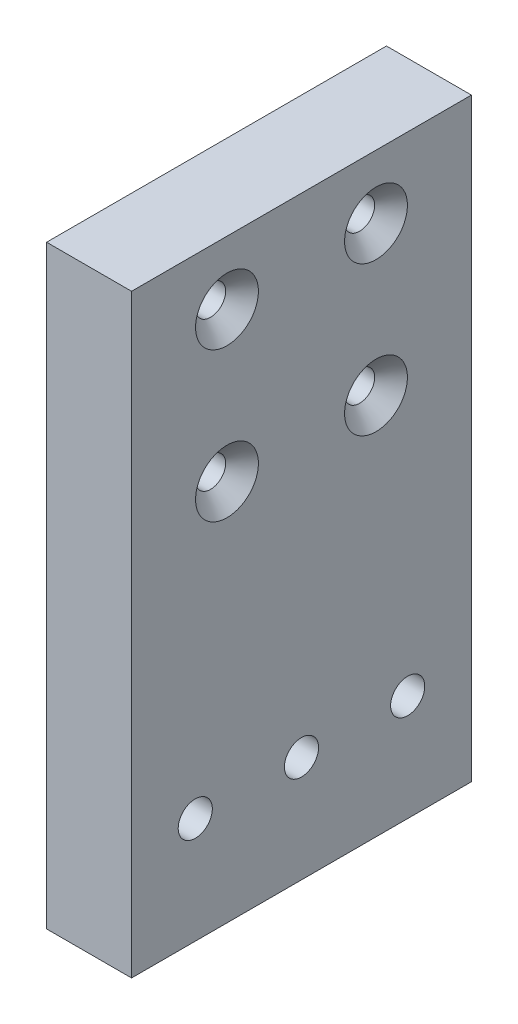
SolidWorks part; units mm, degrees
material "Nylon 6/10"
ref_plane "Front Plane" through (0, 0, 0) normal (0, 0, 1) x (1, 0, 0)
ref_plane "Top Plane" through (0, 0, 0) normal (0, 1, 0) x (1, 0, 0)
ref_plane "Right Plane" through (0, 0, 0) normal (1, 0, 0) x (0, 0, -1)
sketch "Sketch1" plane through (0, 0, 0) normal (1, 0, 0) x (0, 0, -1)
  line L1 (-25.4, -44.45) -> (25.4, -44.45)
  line L2 (-25.4, -44.45) -> (-25.4, 44.45)
  line L3 (-25.4, 44.45) -> (25.4, 44.45)
  line L4 (25.4, -44.45) -> (25.4, 44.45)
  line L5 (-25.4, -44.45) -> (25.4, 44.45) construction
  line L6 (-25.4, 44.45) -> (25.4, -44.45) construction
  point P0 (0, 0)
  dimension "D1" = 50.8
  dimension "D2" = 88.9
extrude "Boss-Extrude1" add sketch "Sketch1" along normal blind 12.7
hole_wizard "CSK for M4 Flat Head Machine Screw1" positions "Sketch3" profile "Sketch2" countersink size "M4" standard "ANSI Metric" end condition through all
sketch "Sketch3" plane through (12.7, 0, 0) normal (1, 0, 0) x (0, 0, -1)
  line L1 (-11.1369, 12.7) -> (11.1369, 12.7) construction
  line L2 (-11.1369, 12.7) -> (-11.1369, 34.9739) construction
  line L3 (-11.1369, 34.9739) -> (11.1369, 34.9739) construction
  line L4 (11.1369, 12.7) -> (11.1369, 34.9739) construction
  line L5 (-11.1369, 12.7) -> (11.1369, 34.9739) construction
  line L6 (-11.1369, 34.9739) -> (11.1369, 12.7) construction
  line L8 (25.4, 44.45) -> (-25.4, 44.45) construction
  point P219 (11.1369, 34.9739)
  point P223 (-11.1369, 34.9739)
  point P225 (-11.1369, 12.7)
  point P227 (11.1369, 12.7)
  dimension "D1" = 31.5
  dimension "D2" = 31.75
sketch "Sketch2" plane through (12.7, 34.9739, -11.1369) normal (0, 1, 0) x (0, 0, -1)
  line L0 (0, 0) -> (0, 12.7)
  line L1 (0, 12.7) -> (2.25, 12.7)
  line L2 (2.25, 12.7) -> (2.25, 2.45)
  line L3 (2.25, 2.45) -> (4.7, 0)
  line L5 (4.7, 0) -> (0, 0)
  line L6 (-2.25, 2.45) -> (-4.7, 0) construction
  line L11 (0, -6.35) -> (0, 107.95) construction
  dimension "Thru Hole Dia." = 4.5
  dimension "Thru Hole Depth" = 12.7
  dimension "Near C'Sink Dia." = 9.4
  dimension "Near C'Sink Angle" = 90
hole_wizard "CBORE for #10 Socket Head Cap Screw1" positions "Sketch5" profile "Sketch4" counterbore size "#10" standard "ANSI Inch" end condition through all
sketch "Sketch5" plane through (0, 0, 0) normal (-1, 0, 0) x (0, 0, 1)
  line L0 (-25.4, -28.575) -> (25.4, -28.575) construction
  line L1 (-25.4, -44.45) -> (-25.4, 44.45) construction
  line L2 (25.4, 44.45) -> (25.4, -44.45) construction
  line L4 (25.4, -44.45) -> (-25.4, -44.45) construction
  line L5 (0, -44.45) -> (0, 0) construction
  point P0 (-15.875, -28.575)
  point P2 (0, -28.575)
  point P4 (15.875, -28.575)
  dimension "D1" = 15.875
  dimension "D2" = 9.525
  dimension "D3" = 9.525
sketch "Sketch4" plane through (0, -28.575, -15.875) normal (0, 1, 0) x (0, 0, 1)
  line L0 (0, 0) -> (0, 12.7)
  line L1 (0, 12.7) -> (2.5527, 12.7)
  line L3 (2.5527, 12.7) -> (2.5527, 4.826)
  line L4 (2.5527, 4.826) -> (4.7625, 4.826)
  line L5 (4.7625, 4.826) -> (4.7625, 0)
  line L7 (4.7625, 0) -> (0, 0)
  line L11 (0, -6.35) -> (0, 107.95) construction
  dimension "Thru Hole Dia." = 5.1054
  dimension "Thru Hole Depth" = 12.7
  dimension "C'Bore Dia." = 9.525
  dimension "C'Bore Depth" = 4.826
